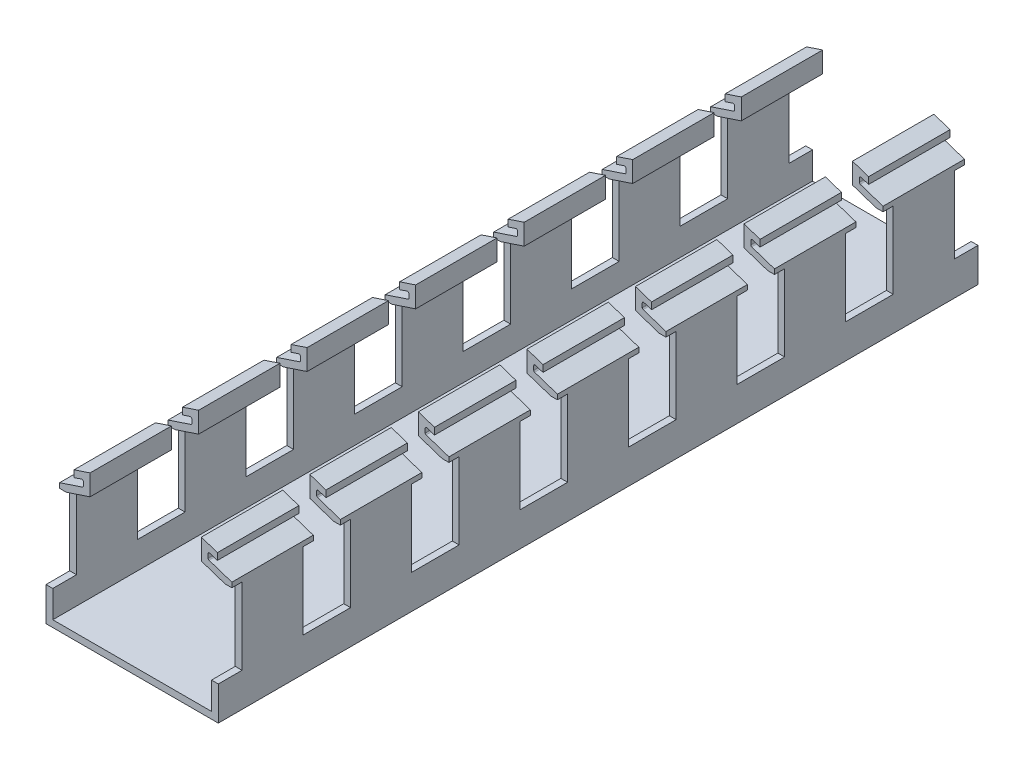
SolidWorks part; units mm, degrees
ref_plane "Alzado" through (0, 0, 0) normal (0, 0, 1) x (1, 0, 0)
ref_plane "Planta" through (0, 0, 0) normal (0, 1, 0) x (1, 0, 0)
ref_plane "Vista lateral" through (0, 0, 0) normal (1, 0, 0) x (0, 0, -1)
sketch "Croquis2" plane through (0, 0, 0) normal (0, 0, 1) x (1, 0, 0)
  line L0 (-12.7, 0) -> (12.7, 0)
  line L1 (0, 0) -> (0, 14.1113) construction
  line L2 (-12.7, 0) -> (-12.7, 17)
  line L4 (8.2, 17.4459) -> (11.7, 16.2792)
  line L5 (8.2, 20.5) -> (8.2, 17.4459)
  line L6 (10.5717, 19.7094) -> (8.2, 20.5)
  line L7 (10.5717, 18.7094) -> (10.5717, 19.7094)
  line L8 (9.2, 18.8892) -> (9.2, 18.3108)
  line L9 (10.5717, 18.7094) -> (9.4632, 19.0789)
  line L10 (-9.3368, 18.1211) -> (-12.7, 17)
  line L11 (-10.5717, 18.7094) -> (-9.4632, 19.0789)
  line L12 (-9.2, 18.8892) -> (-9.2, 18.3108)
  line L13 (9.3368, 18.1211) -> (12.7, 17)
  line L14 (12.7, 0) -> (12.7, 17)
  line L15 (11.7, 16.2792) -> (11.7, 1)
  line L16 (-10.5717, 18.7094) -> (-10.5717, 19.7094)
  line L18 (-10.5717, 19.7094) -> (-8.2, 20.5)
  line L19 (-8.2, 20.5) -> (-8.2, 17.4459)
  line L20 (-8.2, 17.4459) -> (-11.7, 16.2792)
  line L21 (-11.7, 16.2792) -> (-11.7, 1)
  line L22 (-11.7, 1) -> (11.7, 1)
  arc A0 (9.3368, 18.1211) -> (9.2, 18.3108) centre (9.4, 18.3108) cw
  arc A1 (9.2, 18.8892) -> (9.4632, 19.0789) centre (9.4, 18.8892) cw
  arc A4 (-9.2, 18.8892) -> (-9.4632, 19.0789) centre (-9.4, 18.8892) ccw
  arc A5 (-9.3368, 18.1211) -> (-9.2, 18.3108) centre (-9.4, 18.3108) ccw
  dimension "D8" = 0.2
  dimension "D1" = 25.4
  dimension "D2" = 1
  dimension "D3" = 1
  dimension "D4" = 1
  dimension "D5" = 1
  dimension "D6" = 1
  dimension "D7" = 20.5
  dimension "D9" = 8.2
  dimension "D10" = 2.5
  dimension "D11" = 71.565
  dimension "D12" = 3.0541
extrude "Saliente-Extruir1" add sketch "Croquis2" along normal mid plane 16
sketch "Croquis3" plane through (0, 0, 0) normal (1, 0, 0) x (0, 0, -1)
  line L0 (0, 0) -> (0, 24.3686) construction
  line L1 (-8, 0) -> (8, 0) construction
  line L2 (-8, 5) -> (-4.5, 5)
  line L3 (-8, 0) -> (-8, 17) construction
  line L4 (-4.5, 5) -> (-4.5, 16.2792)
  line L5 (-4.5, 16.2792) -> (-6, 16.2792)
  line L6 (-6, 16.2792) -> (-6, 20.5)
  line L7 (-8, 5) -> (-8, 20.5)
  line L8 (-8, 20.5) -> (-6, 20.5)
  line L10 (-8, 20.5) -> (8, 20.5) construction
  line L11 (8, 20.5) -> (6, 20.5)
  line L12 (8, 5) -> (8, 20.5)
  line L13 (6, 16.2792) -> (6, 20.5)
  line L14 (4.5, 16.2792) -> (6, 16.2792)
  line L15 (4.5, 5) -> (4.5, 16.2792)
  line L16 (8, 5) -> (4.5, 5)
  line L17 (-8, 16.2792) -> (8, 16.2792) construction
  dimension "D1" = 5
  dimension "D2" = 3.5
  dimension "D3" = 2
extrude "Cortar-Extruir1" cut sketch "Croquis3" against normal mid plane 66
pattern_linear "MatrizL1" count 7 spacing 16 along (0, 0, -1) of "Saliente-Extruir1", "Cortar-Extruir1"
